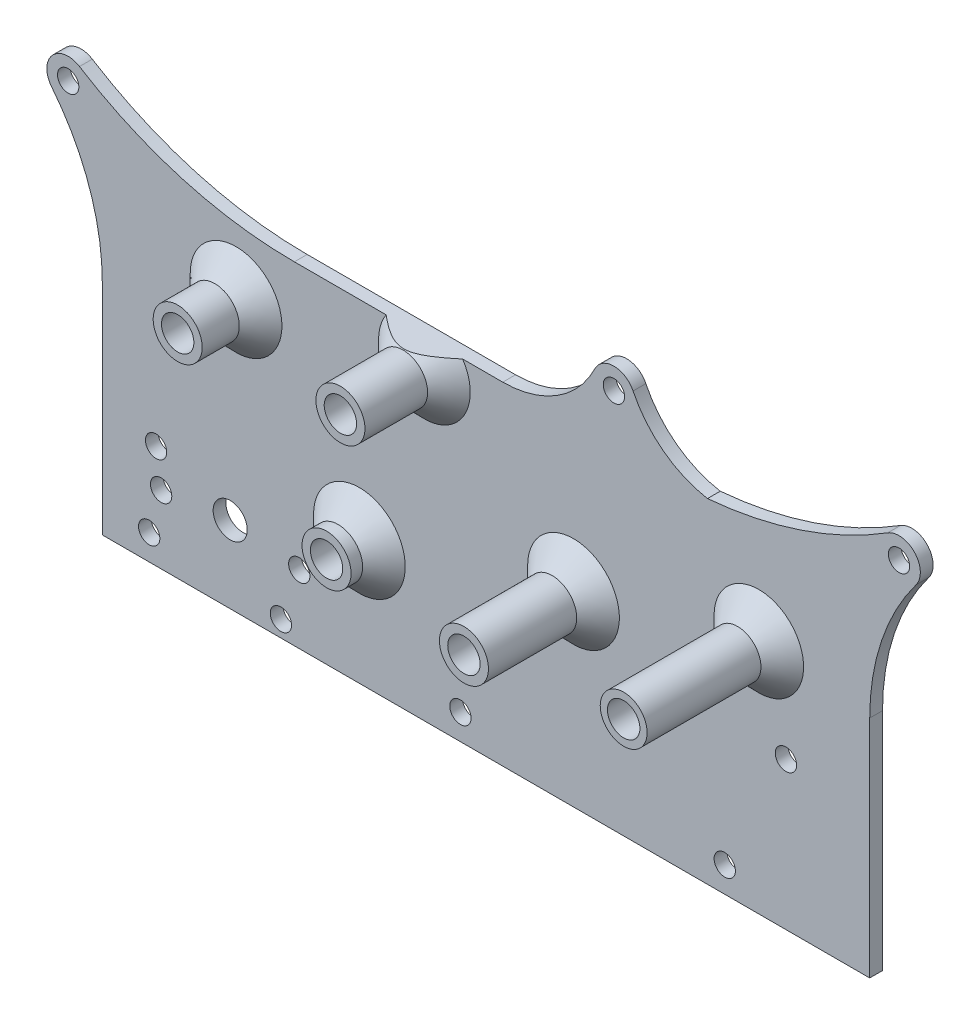
SolidWorks part; units mm, degrees
ref_plane "Front Plane" through (0, 0, 0) normal (0, 0, 1) x (1, 0, 0)
ref_plane "Top Plane" through (0, 0, 0) normal (0, 1, 0) x (1, 0, 0)
ref_plane "Right Plane" through (0, 0, 0) normal (1, 0, 0) x (0, 0, -1)
sketch "Sketch1" plane through (0, 0, 0) normal (0, 0, 1) x (1, 0, 0)
  line L1 (-30, -18) -> (150, -18)
  line L2 (-30, -18) -> (-30, 60)
  line L3 (-30, 60) -> (150, 60)
  line L4 (150, -18) -> (150, 60)
  circle A0 centre (0, 0) radius 4
  dimension "D5" = 8
  dimension "D1" = 78
  dimension "D2" = 18
  dimension "D3" = 150
  dimension "D4" = 30
extrude "Boss-Extrude1" add sketch "Sketch1" along normal blind 3
sketch "Sketch2" plane through (0, 0, 3) normal (0, 0, 1) x (1, 0, 0)
  circle A0 centre (123.9911, 37.416) radius 37.5 construction
  circle A1 centre (45.5529, 54.0886) radius 37.5 construction
  circle A2 centre (1.3796, 45.5021) radius 37.5 construction
  circle A3 centre (123.9911, 37.416) radius 37.5 construction
  circle A4 centre (45.5529, 54.0886) radius 37.5 construction
  circle A5 centre (1.3796, 45.5021) radius 37.5 construction
  circle A6 centre (30.3051, 11.0301) radius 24.75 construction
  circle A7 centre (30.3051, 11.0301) radius 24.75 construction
  circle A8 centre (80.5244, 25.7691) radius 37.5 construction
  circle A9 centre (130.3502, 16.6164) radius 14.25 construction
  circle A10 centre (80.5244, 25.7691) radius 37.5 construction
  circle A11 centre (130.3502, 16.6164) radius 14.25 construction
  circle A12 centre (1.3796, 45.5021) radius 2.5
  circle A13 centre (30.3051, 11.0301) radius 2.5
  circle A14 centre (45.5529, 54.0886) radius 2.5
  circle A15 centre (80.5244, 25.7691) radius 2.5
  circle A16 centre (123.9911, 37.416) radius 2.5
  circle A17 centre (130.3502, 16.6164) radius 2.5
  dimension "D1" = 5
  dimension "D2" = 5
extrude "Cut-Extrude1" cut sketch "Sketch2" against normal blind 3
sketch "Sketch3" plane through (0, 0, 3) normal (0, 0, 1) x (1, 0, 0)
  circle A0 centre (123.9911, 37.416) radius 10
  dimension "D1" = 20
extrude "Cut-Extrude2" [suppressed] cut sketch "Sketch3" against normal blind 3
sketch "Sketch4" plane through (0, 0, 3) normal (0, 0, 1) x (1, 0, 0)
  line L0 (-30, -18) -> (150, -18) construction
  circle A0 centre (54, -12) radius 5 construction
  circle A1 centre (54, -12) radius 2.5
  circle A2 centre (-19, -12) radius 5 construction
  circle A3 centre (-19, -12) radius 2.5
  circle A4 centre (116, -12) radius 5 construction
  circle A5 centre (116, -12) radius 2.5
  dimension "D1" = 10
  dimension "D2" = 5
  dimension "D6" = 5
  dimension "D7" = 10
  dimension "D9" = 5
  dimension "D10" = 10
  dimension "D3" = 6
  dimension "D4" = 54
  dimension "D5" = 6
  dimension "D8" = 19
  dimension "D11" = 6
  dimension "D12" = 116
extrude "Cut-Extrude3" cut sketch "Sketch4" against normal blind 10
sketch "Sketch5" plane through (0, 0, 3) normal (0, 0, 1) x (1, 0, 0)
  line L0 (150, 60) -> (-30, 60) construction
  line L1 (116.0681, 60) -> (116.0681, 53.2935)
  line L2 (116.0681, 53.2935) -> (63.9319, 53.2935)
  line L3 (63.9319, 53.2935) -> (63.9319, 60)
  line L4 (-38, 70.2305) -> (0, 0) construction
  line L5 (-38, 70.2305) -> (-19, -12) construction
  line L6 (-38, 70.2305) -> (90, 71.2935) construction
  line L7 (-38, 70.2305) -> (45.5529, 54.0886) construction
  line L8 (-38, 70.2305) -> (1.3796, 45.5021) construction
  line L9 (-30, 33.2846) -> (-30, -18) construction
  line L10 (15.0485, 60) -> (-9.6297, 52.4155)
  line L11 (-9.6297, 52.4155) -> (-30, 33.2846)
  circle A0 centre (90, 71.2935) radius 2.5
  circle A1 centre (90, 71.2935) radius 5 construction
  circle A2 centre (90, 71.2935) radius 7.5 construction
  circle A3 centre (-38, 70.2305) radius 2.5
  circle A4 centre (-38, 70.2305) radius 5 construction
  circle A5 centre (-38, 70.2305) radius 7.5 construction
  circle A6 centre (80.5244, 25.7691) radius 39 construction
  circle A7 centre (80.5244, 25.7691) radius 39 construction
  arc A8 (85.5055, 73.4842) -> (94.4945, 73.4842) centre (90, 71.2935) cw
  circle A9 centre (123.9911, 37.416) radius 37.5 construction
  circle A10 centre (123.9911, 37.416) radius 37.5 construction
  circle A11 centre (123.9911, 37.416) radius 39 construction
  circle A12 centre (1.3796, 45.5021) radius 39 construction
  circle A13 centre (63.9319, 84) radius 24 construction
  circle A14 centre (116.0681, 84) radius 24 construction
  arc A15 (116.0681, 60) -> (94.4945, 73.4842) centre (116.0681, 84) cw
  arc A16 (63.9319, 60) -> (85.5055, 73.4842) centre (63.9319, 84) ccw
  arc A17 (-41.8983, 67.0995) -> (-30, 33.2846) centre (-84, 33.2846) cw
  arc A18 (-35.3476, 74.469) -> (15.0485, 60) centre (15.0485, 155) ccw
  arc A19 (-35.3476, 74.469) -> (-41.8983, 67.0995) centre (-38, 70.2305) ccw
  dimension "D1" = 5
  dimension "D2" = 10
  dimension "D3" = 15
  dimension "D6" = 48
  dimension "D8" = 54
  dimension "D9" = 95
  dimension "D10" = 7.9243
  dimension "D4" = 90
  dimension "D5" = 38
  dimension "D7" = 18
  dimension "D11" = 13
extrude "Boss-Extrude2" add sketch "Sketch5" against normal blind 3
sketch "Sketch6" plane through (0, 0, 3) normal (0, 0, 1) x (1, 0, 0)
  line L0 (123.9911, 37.416) -> (156.8716, 70.2965) construction
  line L1 (-30, -18) -> (150, -18) construction
  line L2 (150, 60) -> (116.0681, 60) construction
  line L3 (150, -18) -> (150, 60) construction
  line L4 (103.7179, 60) -> (150, 34.8012)
  circle A0 centre (123.9911, 37.416) radius 39 construction
  circle A1 centre (156.8716, 70.2965) radius 7.5 construction
  circle A2 centre (156.8716, 70.2965) radius 5 construction
  circle A3 centre (156.8716, 70.2965) radius 2.5
  arc A4 (103.7179, 60) -> (154.2139, 74.5316) centre (103.7179, 155) ccw
  arc A5 (160.8655, 67.2884) -> (150, 34.8012) centre (204, 34.8012) ccw
  arc A6 (154.2139, 74.5316) -> (160.8655, 67.2884) centre (156.8716, 70.2965) cw
  dimension "D1" = 15
  dimension "D2" = 10
  dimension "D3" = 5
  dimension "D5" = 54
  dimension "D6" = 95
  dimension "D4" = 45
extrude "Boss-Extrude3" add sketch "Sketch6" against normal blind 3
sketch "Sketch7" plane through (0, 0, 3) normal (0, 0, 1) x (1, 0, 0)
  circle A0 centre (11.8916, -14.1718) radius 2.5 construction
  circle A1 centre (11.8916, -14.1718) radius 2.5
  circle A2 centre (-17.3843, 6.3274) radius 2.5 construction
  circle A3 centre (-17.3843, 6.3274) radius 2.5
extrude "Cut-Extrude4" cut sketch "Sketch7" against normal through all
sketch "Sketch8" plane through (0, 0, 3) normal (0, 0, 1) x (1, 0, 0)
  circle A0 centre (1.3796, 45.5021) radius 3.8
  circle A1 centre (1.3796, 45.5021) radius 5.75
  dimension "D1" = 7.6
  dimension "D2" = 11.5
extrude "Boss-Extrude4" add sketch "Sketch8" along normal blind 13.7
sketch "Sketch9" plane through (0, 0, 3) normal (0, 0, 1) x (1, 0, 0)
  circle A0 centre (30.3051, 11.0301) radius 5.75
  circle A1 centre (30.3051, 11.0301) radius 3.8
  dimension "D1" = 7.6
  dimension "D2" = 11.5
extrude "Boss-Extrude5" add sketch "Sketch9" along normal blind 7.7
sketch "Sketch10" plane through (0, 0, 3) normal (0, 0, 1) x (1, 0, 0)
  circle A0 centre (45.5529, 54.0886) radius 5.75
  circle A1 centre (45.5529, 54.0886) radius 3.8
  dimension "D1" = 7.6
  dimension "D2" = 11.5
extrude "Boss-Extrude6" add sketch "Sketch10" along normal blind 19.7
sketch "Sketch11" plane through (0, 0, 3) normal (0, 0, 1) x (1, 0, 0)
  circle A0 centre (80.5244, 25.7691) radius 3.8
  circle A1 centre (80.5244, 25.7691) radius 5.75
  dimension "D1" = 7.6
  dimension "D2" = 11.5
extrude "Boss-Extrude7" add sketch "Sketch11" along normal blind 25.7
chamfer "Chamfer1" distance 5 angle 45 4 edges at (-4.3704, 45.5021, 3) (24.5551, 11.0301, 3) (39.8029, 54.0886, 3) (74.7744, 25.7691, 3)
sketch "Sketch12" plane through (0, 0, 3) normal (0, 0, 1) x (1, 0, 0)
  circle A0 centre (123.9911, 37.416) radius 5.5
  circle A1 centre (123.9911, 37.416) radius 3.8
  dimension "D1" = 7.6
  dimension "D2" = 11
extrude "Boss-Extrude8" add sketch "Sketch12" along normal blind 31.7
chamfer "Chamfer2" distance 5 angle 45 1 edges at (118.4911, 37.416, 3)
sketch "Sketch13" plane through (0, 0, 0) normal (0, 0, -1) x (-1, 0, 0)
  line L0 (-12.2, -2) -> (-12.2, 4) construction
  line L1 (-12.2, -2) -> (-12.2, 4) construction
  line L2 (12.2, 4) -> (12.2, 1) construction
  line L3 (12.2, 4) -> (12.2, 1) construction
  line L4 (30, -18) -> (-150, -18) construction
  circle A0 centre (-16.2, -2) radius 2.5
  circle A1 centre (16.2, -2) radius 2.5
  circle A2 centre (16.2, -2) radius 4 construction
  circle A3 centre (-16.2, -2) radius 4 construction
  dimension "D1" = 5
  dimension "D2" = 8
  dimension "D3" = 16
extrude "Cut-Extrude5" cut sketch "Sketch13" against normal through all
equation "\"hole_diameter\"=7.6"
equation "\"D1@Sketch10\"=\"hole_diameter\""
equation "\"D1@Sketch11\"=\"hole_diameter\""
equation "\"D1@Sketch12\"=\"hole_diameter\""
equation "\"outer_diameter\"=11"
equation "\"D2@Sketch12\"=\"outer_diameter\""
